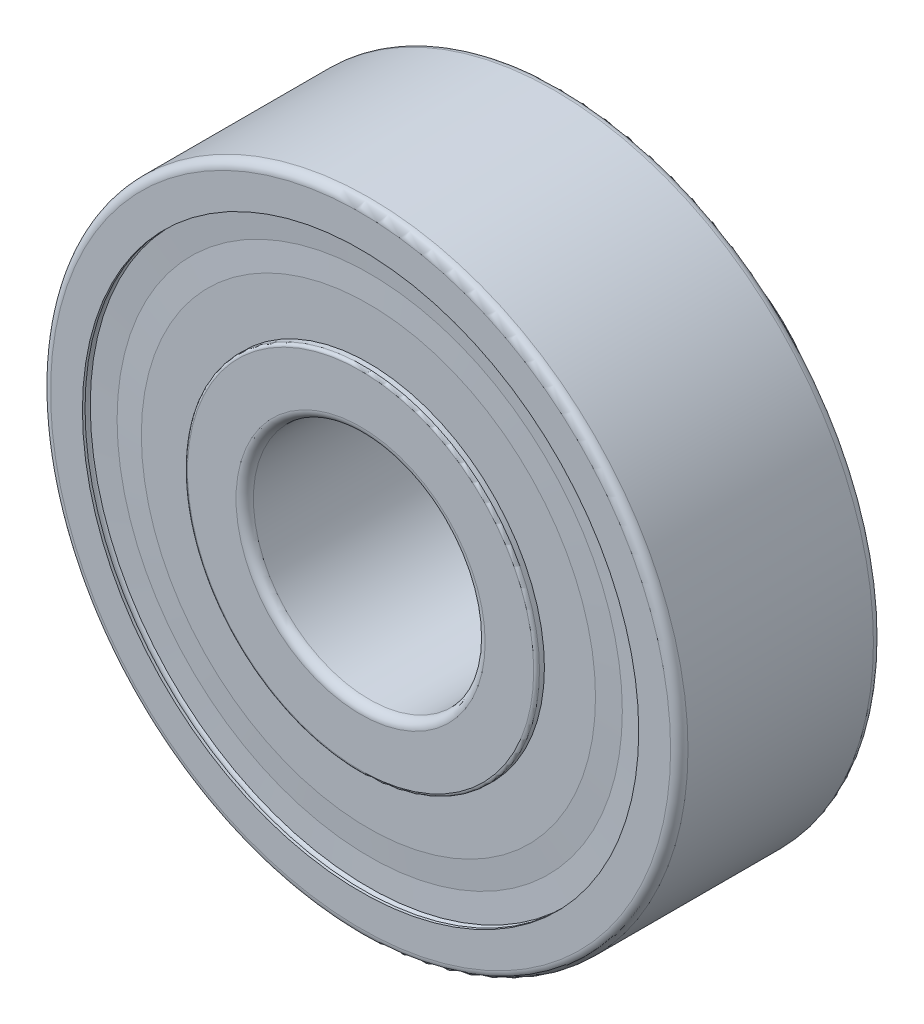
SolidWorks part; units mm, degrees
ref_plane "Front Plane" through (0, 0, 0) normal (0, 0, 1) x (1, 0, 0)
ref_plane "Top Plane" through (0, 0, 0) normal (0, 1, 0) x (1, 0, 0)
ref_plane "Right Plane" through (0, 0, 0) normal (1, 0, 0) x (0, 0, -1)
sketch "Sketch1" plane through (0, 0, 0) normal (1, 0, 0) x (0, 0, -1)
  line L0 (-3.2, 4) -> (3.2, 4)
  line L1 (0, 9.3345) -> (0, 11) construction
  line L2 (3.5, 5.975) -> (3.5, 5.55)
  line L3 (0, 0) -> (0, 4) construction
  line L4 (-3.5, 0) -> (3.5, 0) construction
  line L5 (-1.5207, 6.075) -> (-3.14, 6.075)
  line L6 (-3.5, 5.975) -> (-3.5, 4.3)
  line L7 (0, 4) -> (0, 5.3655) construction
  line L8 (-3.14, 6.075) -> (-3.05, 7.8375)
  line L9 (-3.05, 7.8375) -> (-3.05, 8.7188)
  line L10 (-3.05, 8.7188) -> (-3.14, 9.6)
  line L11 (-3.14, 9.6) -> (-3.23, 9.6)
  line L12 (-3.23, 9.6) -> (-3.185, 8.7188)
  line L13 (-3.185, 8.7188) -> (-3.23, 7.8375)
  line L14 (-3.23, 7.8375) -> (-3.23, 6.075)
  line L15 (-3.23, 6.075) -> (-3.4, 6.075)
  line L16 (3.23, 6.075) -> (3.4, 6.075)
  line L17 (3.23, 7.8375) -> (3.23, 6.075)
  line L18 (3.185, 8.7188) -> (3.23, 7.8375)
  line L19 (3.23, 9.6) -> (3.185, 8.7188)
  line L20 (3.14, 9.6) -> (3.23, 9.6)
  line L21 (3.05, 8.7188) -> (3.14, 9.6)
  line L22 (3.05, 7.8375) -> (3.05, 8.7188)
  line L23 (3.14, 6.075) -> (3.05, 7.8375)
  line L24 (1.5207, 6.075) -> (3.14, 6.075)
  line L25 (-3.5, 9.6) -> (-3.5, 10.7)
  line L26 (-3.2, 11) -> (3.2, 11)
  line L27 (3.5, 9.6) -> (3.5, 10.7)
  line L28 (3.41, 9.6) -> (3.5, 9.6)
  line L29 (2.9089, 8.8) -> (3.05, 9.6)
  line L30 (1.3549, 8.8) -> (2.9089, 8.8)
  line L31 (-2.9089, 8.8) -> (-3.05, 9.6)
  line L32 (3.6, 5.45) -> (7.25, 5.45)
  line L33 (-3.41, 9.6) -> (-3.5, 9.6)
  line L34 (3.5, 5.45) -> (3.5, 4.3) construction
  line L35 (-1.3549, 8.8) -> (-2.9089, 8.8)
  line L36 (3.2, 4) -> (7.05, 4)
  line L37 (7.35, 4.3) -> (7.35, 5.35)
  line L38 (3.5, 5.55) -> (3.6, 5.45)
  arc A0 (-1.5207, 6.075) -> (1.5207, 6.075) centre (0, 7.35) ccw
  arc A1 (-3.5, 10.7) -> (-3.2, 11) centre (-3.2, 10.7) cw
  arc A2 (-3.4, 6.075) -> (-3.5, 5.975) centre (-3.4, 5.975) ccw
  arc A3 (3.2, 4) -> (3.5, 4.3) centre (3.2, 4.3) ccw construction
  arc A4 (-3.2, 4) -> (-3.5, 4.3) centre (-3.2, 4.3) cw
  arc A5 (-3.05, 9.6) -> (-3.41, 9.6) centre (-3.23, 9.6) ccw
  arc A6 (3.4, 6.075) -> (3.5, 5.975) centre (3.4, 5.975) cw
  arc A7 (1.3549, 8.8) -> (-1.3549, 8.8) centre (0, 7.35) ccw
  arc A8 (3.5, 10.7) -> (3.2, 11) centre (3.2, 10.7) ccw
  arc A9 (3.05, 9.6) -> (3.41, 9.6) centre (3.23, 9.6) cw
  arc A10 (7.05, 4) -> (7.35, 4.3) centre (7.05, 4.3) ccw
  arc A11 (7.25, 5.45) -> (7.35, 5.35) centre (7.25, 5.35) cw
  point P16 (-3.5, 6.075)
  point P19 (3.5, 4)
  point P22 (-3.5, 4)
  point P65 (7.35, 5.45)
  dimension "D2" = 1.9845
  dimension "D6" = 3.5
  dimension "D7" = 0.3
  dimension "D12" = 0.1
  dimension "D18" = 0.18
  dimension "D22" = 3.85
  dimension "D1" = 8
  dimension "D3" = 7
  dimension "D4" = 12.15
  dimension "D5" = 14.7
  dimension "D8" = 0.045
  dimension "D9" = 0.18
  dimension "D10" = 0.09
  dimension "D11" = 0.09
  dimension "D13" = 6.46
  dimension "D14" = 15.675
  dimension "D15" = 17.4375
  dimension "D16" = 19.2
  dimension "D17" = 22
  dimension "D19" = 0.09
  dimension "D20" = 100
  dimension "D21" = 17.6
  dimension "D23" = 10.9
revolve "Bearing Body" add sketch "Sketch1" angle 360 about L4
ref_axis "Rotation Axis" through (0, 0, -7.05) along (0, 0, 1)
sketch "Sketch2" plane through (0, 0, 0) normal (1, 0, 0) x (0, 0, -1)
  line L0 (1.9845, 7.35) -> (-1.9845, 7.35)
  line L1 (0, 0) -> (0, 7.35) construction
  arc A0 (-1.9845, 7.35) -> (1.9845, 7.35) centre (0, 7.35) ccw
  arc A1 (-1.5207, 6.075) -> (1.5207, 6.075) centre (0, 7.35) ccw construction
  dimension "D1" = 3.969
revolve "Ball" add sketch "Sketch2" angle 360 about L0
pattern_circular "Ball Pattern" count 7 over 360 about axis through (0, 0, -7.05) along (0, 0, 1) of bodies 104
ref_plane "Set Screw Hole Plane" through (0, 5.45, 0) normal (0, 1, 0) x (1, 0, 0)
sketch "Set Screw Hole Reference" plane through (0, 5.45, 0) normal (0, 1, 0) x (1, 0, 0)
  line L0 (0, 3.5) -> (0, 5.425) construction
  line L1 (10.7, 3.5) -> (-10.7, 3.5) construction
  line L2 (0, 5.425) -> (0, 7.35) construction
  line L3 (5.35, 7.35) -> (-5.35, 7.35) construction
  circle A0 centre (0, 5.425) radius 1.25 construction
  dimension "D1" = 2.5
hole_wizard "M3 Set Screw Hole" positions "Sketch7" profile "Sketch6" tap size "M3" standard "ISO"
sketch "Sketch7" plane through (0, 5.45, 0) normal (0, 1, 0) x (1, 0, 0)
  point P0 (0, 5.425)
sketch "Sketch6" plane through (0, 5.45, -5.425) normal (1, 0, 0) x (0, 0, 1)
  line L0 (0, 0) -> (0, 8.2511)
  line L1 (0, 8.2511) -> (1.25, 7.5)
  line L2 (1.25, 7.5) -> (1.25, 0)
  line L5 (1.25, 0) -> (0, 0)
  line L10 (0, 8.2511) -> (-1.25, 7.5) construction
  line L11 (0, -6.35) -> (0, 107.95) construction
  dimension "Tap Drill Dia." = 2.5
  dimension "Tap Drill Depth" = 7.5
  dimension "Drill Angle" = 118
pattern_circular "M3 Set Screw Hole Pattern" count 2 every 90 about axis through (0, 0, -7.05) along (0, 0, 1) of "M3 Set Screw Hole" reverse direction yes
